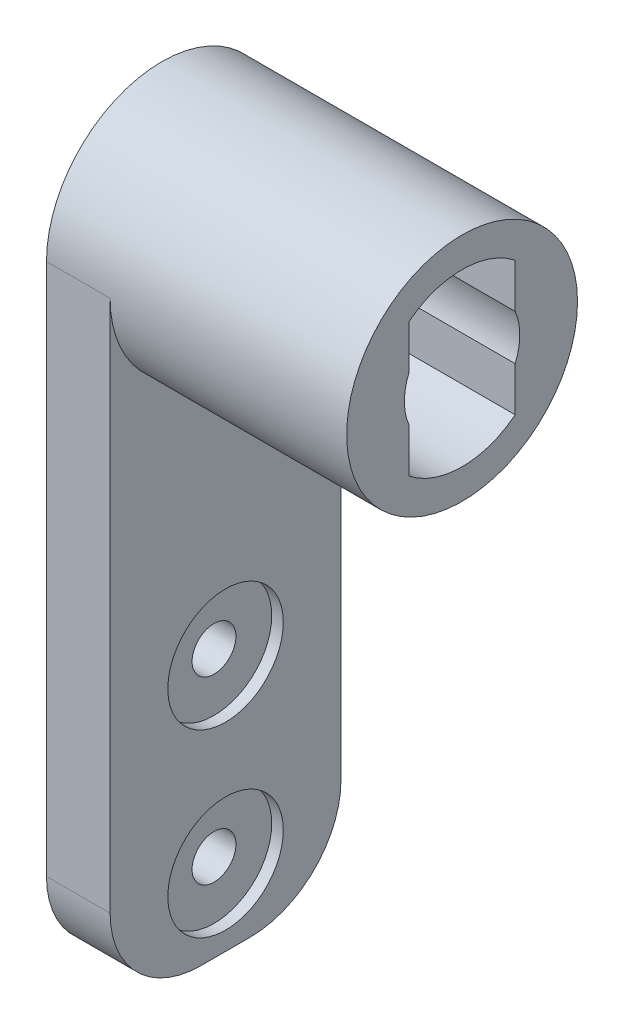
SolidWorks part; units mm, degrees
material "ABS"
ref_plane "Front Plane" through (0, 0, 0) normal (1, 0, 0) x (0, 1, 0)
ref_plane "Top Plane" through (0, 0, 0) normal (0, 0, 1) x (0, 1, 0)
ref_plane "Right Plane" through (0, 0, 0) normal (0, 1, 0) x (-1, 0, 0)
sketch "Sketch1" plane through (0, 0, 0) normal (1, 0, 0) x (0, 1, 0)
  circle A0 centre (0, 0) radius 3.175
  circle A1 centre (0, 0) radius 3
  circle A2 centre (0, 0) radius 6.35
  dimension "D1" = 6
  dimension "D2" = 6.35
  dimension "D3" = 12.7
extrude "Boss-Extrude1" add sketch "Sketch1" along normal blind 16.51 contours A2 A0 region at (0, -6.1704, 0)
ref_plane "Plane1" through (0, 0, 6.35) normal (0, 0, 1) x (0, 1, 0)
sketch "Sketch10" plane through (0, 0, 0) normal (-1, 0, 0) x (0, -1, 0)
  line L0 (0, 6.35) -> (34.29, 6.35)
  line L1 (14.575, 6.35) -> (-14.575, 6.35) construction
  line L2 (34.29, 6.35) -> (34.29, -6.35)
  line L3 (34.29, -6.35) -> (0, -6.35)
  circle A0 centre (0, 0) radius 6.35 construction
  arc A2 (0, 6.35) -> (0, -6.35) centre (0, 0) cw
  point P8 (0, 0)
  point P9 (0, 0)
  point P10 (0, 0)
  dimension "D1" = 34.29
extrude "Boss-Extrude3" add sketch "Sketch10" against normal blind 3.5 contours L0 A2 L3 L2 region at (0, -19.6044, 0)
fillet "Fillet2" radius 5 2 edges at (1.75, -34.29, 6.35) (1.75, -34.29, -6.35)
sketch "Sketch11" plane through (0, 0, 0) normal (-1, 0, 0) x (0, -1, 0)
  line L0 (34.29, 0) -> (0, 0) construction
  line L1 (34.29, 1.35) -> (34.29, -1.35) construction
  circle A0 centre (30.099, 0) radius 1.2065
  circle A1 centre (20.193, 0) radius 1.2065
  dimension "D3" = 2.413
  dimension "D1" = 4.191
  dimension "D2" = 9.906
extrude "Cut-Extrude1" cut sketch "Sketch11" against normal through all
sketch "Sketch12" plane through (3.5, 0, 0) normal (1, 0, 0) x (0, 1, 0)
  circle A0 centre (-20.193, 0) radius 3.175
  circle A1 centre (-30.099, 0) radius 3.175
  dimension "D1" = 6.35
extrude "Cut-Extrude2" cut sketch "Sketch12" against normal blind 0.635
sketch "Sketch13" plane through (16.51, 0, 0) normal (1, 0, 0) x (0, 1, 0)
  line L1 (-3.6808, -2.921) -> (3.6808, -2.921)
  line L2 (-3.6808, -2.921) -> (-3.6808, 2.921)
  line L3 (-3.6808, 2.921) -> (3.6808, 2.921)
  line L4 (3.6808, -2.921) -> (3.6808, 2.921)
  line L5 (-3.6808, -2.921) -> (3.6808, 2.921) construction
  line L6 (-3.6808, 2.921) -> (3.6808, -2.921) construction
  circle A0 centre (0, 0) radius 4.699
  circle M5 centre (0, 0) radius 3.175
  dimension "D1" = 9.398
  dimension "D2" = 5.842
extrude "Cut-Extrude3" cut sketch "Sketch13" against normal blind 10.16 contours L2 A0 | L3 L1 M5 | L3 L2 L1 M5 | L1 L4 L3 M5 | L4 A0 region at (16.51, -3.6175, 0) region at (16.51, -4.0921, 0) region at (16.51, 0, 0) region at (16.51, 2.4626, -2.8577) region at (16.51, 4.0921, 0)
